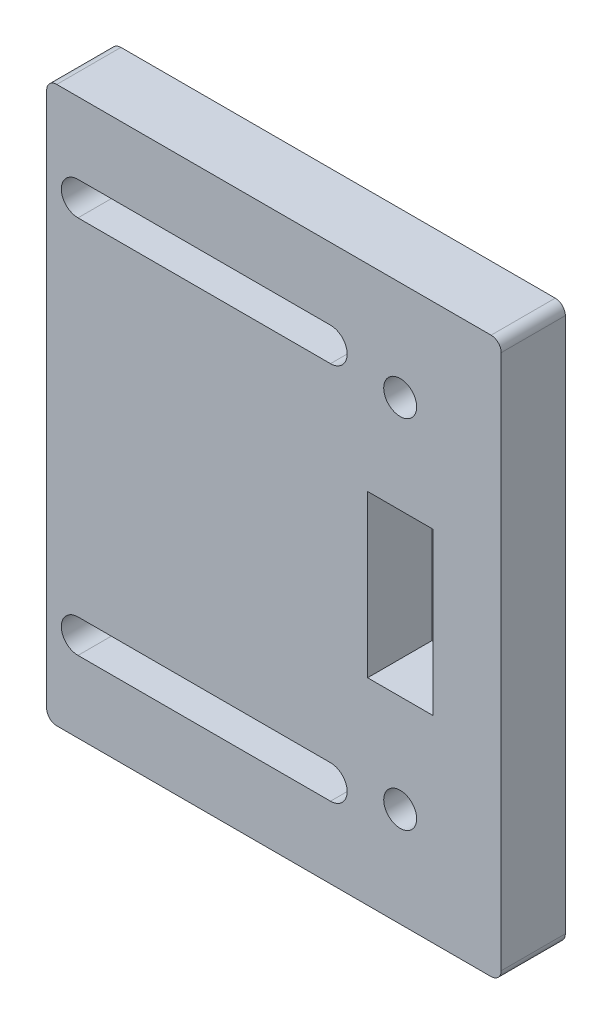
SolidWorks part; units mm, degrees
ref_plane "Front Plane" through (0, 0, 0) normal (0, 0, 1) x (1, 0, 0)
ref_plane "Top Plane" through (0, 0, 0) normal (0, 1, 0) x (1, 0, 0)
ref_plane "Right Plane" through (0, 0, 0) normal (1, 0, 0) x (0, 0, -1)
sketch "Sketch1" plane through (0, 0, 0) normal (0, 0, 1) x (1, 0, 0)
  line L0 (70, -110) -> (70, -90.31) construction
  line L1 (0, 0) -> (90, 0)
  line L2 (0, 0) -> (0, -110)
  line L3 (0, -110) -> (90, -110)
  line L4 (90, 0) -> (90, -110)
  line L6 (70, -39.0256) -> (76.45, -39.0256)
  line L8 (76.45, -70.9756) -> (70, -70.9756)
  line L9 (70, -70.9756) -> (63.55, -70.9756)
  line L10 (63.55, -70.9756) -> (63.55, -39.0256)
  line L11 (63.55, -39.0256) -> (70, -39.0256)
  line L12 (80, 0) -> (80, -19.69) construction
  line L14 (76.45, -39.0256) -> (76.45, -55.0006)
  line L15 (76.45, -55.0006) -> (76.45, -70.9756)
  dimension "D6" = 10
  dimension "D1" = 110
  dimension "D2" = 31.95
  dimension "D3" = 12.9
  dimension "D4" = 19.69
  dimension "D5" = 19.69
  dimension "D7" = 90
  dimension "D8" = 80
  dimension "D9" = 13.55
  dimension "D10" = 39.0244
  dimension "D11" = 10
extrude "Boss-Extrude2" add sketch "Sketch1" along normal blind 12.7
sketch "Sketch8" plane through (0, 0, 0) normal (0, 0, -1) x (-1, 0, 0)
  line L1 (-70, -110) -> (-70, -90.31) construction
  dimension "D1" = 19.69
  dimension "D2" = 20
hole_wizard "CSK for 1/4 Flat Head Machine Screw3" positions "Sketch9" profile "Sketch10" countersink size "1/4" standard "ANSI Inch" end condition through all
sketch "Sketch9" plane through (0, 0, 0) normal (0, 0, -1) x (-1, 0, 0)
  point P0 (-70, -90.31)
sketch "Sketch10" plane through (70, -90.31, 0) normal (1, 0, 0) x (0, 1, 0)
  line L0 (0, 0) -> (0, 12.7)
  line L1 (0, 12.7) -> (3.2639, 12.7)
  line L2 (3.2639, 12.7) -> (3.2639, 3.6524)
  line L3 (3.2639, 3.6524) -> (6.4389, 0)
  line L5 (6.4389, 0) -> (0, 0)
  line L6 (-3.2639, 3.6524) -> (-6.4389, 0) construction
  line L11 (0, -6.35) -> (0, 107.95) construction
  dimension "Thru Hole Dia." = 6.5278
  dimension "Thru Hole Depth" = 12.7
  dimension "Near C'Sink Dia." = 12.8778
  dimension "Near C'Sink Angle" = 82
sketch "Sketch11" plane through (0, 0, 0) normal (0, 0, -1) x (-1, 0, 0)
  line L0 (-70, 0) -> (-70, -19.69)
  point P2 (0, 0)
  dimension "D1" = 19.69
  dimension "D2" = 20
hole_wizard "CSK for 1/4 Flat Head Machine Screw4" positions "Sketch12" profile "Sketch13" countersink size "1/4" standard "ANSI Inch" end condition through all
sketch "Sketch12" plane through (0, 0, 0) normal (0, 0, -1) x (-1, 0, 0)
  point P0 (-70, -19.69)
sketch "Sketch13" plane through (70, -19.69, 0) normal (1, 0, 0) x (0, 1, 0)
  line L0 (0, 0) -> (0, 12.7)
  line L1 (0, 12.7) -> (3.2639, 12.7)
  line L2 (3.2639, 12.7) -> (3.2639, 3.6524)
  line L3 (3.2639, 3.6524) -> (6.4389, 0)
  line L5 (6.4389, 0) -> (0, 0)
  line L6 (-3.2639, 3.6524) -> (-6.4389, 0) construction
  line L11 (0, -6.35) -> (0, 107.95) construction
  dimension "Thru Hole Dia." = 6.5278
  dimension "Thru Hole Depth" = 12.7
  dimension "Near C'Sink Dia." = 12.8778
  dimension "Near C'Sink Angle" = 82
fillet "Fillet1" radius 2 4 edges at (0, 0, 6.35) (90, 0, 6.35) (0, -110, 6.35) (90, -110, 6.35)
sketch "Sketch15" plane through (0, 0, 0) normal (0, 0, -1) x (-1, 0, 0)
  line L0 (-56.2003, -14.185) -> (-6.2003, -14.185)
  line L1 (-56.2003, -20.785) -> (-6.2003, -20.785)
  line L2 (0, -55) -> (-82.6046, -55) construction
  line L3 (0, -2) -> (0, -108) construction
  line L4 (-56.2003, -89.215) -> (-6.2003, -89.215)
  line L5 (-56.2003, -95.815) -> (-6.2003, -95.815)
  arc A0 (-6.2003, -14.185) -> (-6.2003, -20.785) centre (-6.2003, -17.485) cw
  arc A1 (-56.2003, -20.785) -> (-56.2003, -14.185) centre (-56.2003, -17.485) cw
  arc A2 (-6.2003, -95.815) -> (-6.2003, -89.215) centre (-6.2003, -92.515) ccw
  arc A3 (-56.2003, -89.215) -> (-56.2003, -95.815) centre (-56.2003, -92.515) ccw
  dimension "D3" = 3.3
  dimension "D4" = 68.43
  dimension "D1" = 50
  dimension "D2" = 50
extrude "Cut-Extrude1" cut sketch "Sketch15" against normal through all
